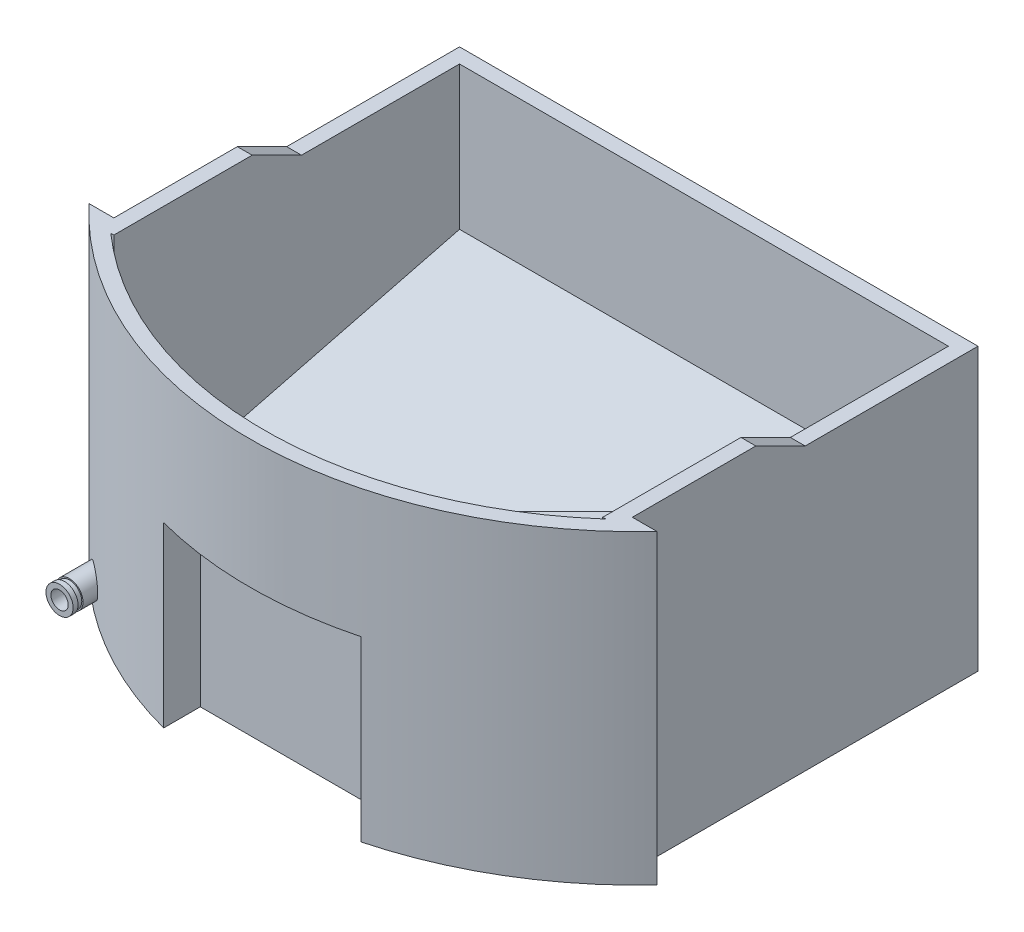
SolidWorks part; units mm, degrees
ref_plane "Front Plane" through (0, 0, 0) normal (0, 0, 1) x (1, 0, 0)
ref_plane "Top Plane" through (0, 0, 0) normal (0, 1, 0) x (1, 0, 0)
ref_plane "Right Plane" through (0, 0, 0) normal (1, 0, 0) x (0, 0, -1)
sketch "Sketch4" plane through (0, 0, 0) normal (0, 1, 0) x (1, 0, 0)
  line L0 (-6.35, 0) -> (139.7, 0)
  line L1 (0, 0) -> (133.35, 0)
  line L2 (0, 0) -> (0, 88.9)
  line L3 (0, 88.9) -> (133.35, 88.9)
  line L4 (133.35, 0) -> (133.35, 88.9)
  arc A1 (-6.35, 0) -> (139.7, 0) centre (66.675, 68.1037) ccw
  point P6 (66.675, -31.75)
  point P9 (66.675, 0)
  dimension "D1" = 133.35
  dimension "D2" = 88.9
  dimension "D3" = 146.05
  dimension "D4" = 6.35
  dimension "D5" = 31.75
extrude "Boss-Extrude2" add sketch "Sketch4" along normal blind 78.74 contours L0 A1 | L0 L4 L3 L2 region at (66.675, 0, 12.8907) region at (66.675, 0, -44.45)
sketch "Sketch5" plane through (0, 0, 0) normal (1, 0, 0) x (0, 0, -1)
  line L0 (0, 78.74) -> (88.9, 78.74) construction
  line L1 (0, 78.74) -> (88.9, 78.74)
  line L2 (88.9, 78.74) -> (88.9, 72.39)
  line L3 (88.9, 78.74) -> (88.9, 0) construction
  line L4 (88.9, 72.39) -> (44.45, 72.39)
  line L5 (44.45, 72.39) -> (31.75, 78.74)
  line L6 (31.75, 78.74) -> (88.9, 78.74)
  dimension "D1" = 12.7
  dimension "D2" = 44.45
  dimension "D3" = 6.35
extrude "Cut-Extrude4" cut sketch "Sketch5" along normal through all contours L2 L4 L5 L6
ref_plane "Plane1" through (3.81, 0, 0) normal (1, 0, 0) x (0, 0, -1)
ref_plane "Plane2" through (129.54, 0, 0) normal (1, 0, 0) x (0, 0, -1)
ref_plane "Plane3" through (0, 0, -85.09) normal (0, 0, -1) x (-1, 0, 0)
ref_plane "Plane4" through (0, 15.24, 0) normal (0, 1, 0) x (1, 0, 0)
ref_plane "Plane5" through (0, 0, 28.448) normal (0, 0, 1) x (1, 0, 0)
ref_plane "Plane6" through (8.89, 0, 0) normal (1, 0, 0) x (0, 0, -1)
ref_plane "Plane7" through (0, 0, -5.08) normal (0, 0, 1) x (1, 0, 0)
shell "Shell1" thickness 3.81 removed face at (66.675, 78.74, -5.2917) removed face at (66.675, 75.565, -38.1) removed face at (66.675, 72.39, -66.675)
sketch "Sketch8" plane through (0, 15.24, 0) normal (0, 1, 0) x (1, 0, 0)
  line L0 (0, 88.9) -> (133.35, 88.9) construction
  line L1 (133.35, 0) -> (133.35, 88.9) construction
  line L2 (-6.35, 0) -> (139.7, 0) construction
  line L3 (0, 0) -> (0, 88.9) construction
  line L4 (0, 88.9) -> (133.35, 88.9)
  line L5 (133.35, 0) -> (133.35, 88.9)
  line L6 (-6.35, 0) -> (139.7, 0)
  line L7 (0, 0) -> (0, 88.9)
  arc A0 (-6.35, 0) -> (139.7, 0) centre (66.675, 68.1037) ccw construction
  arc A1 (-6.35, 0) -> (139.7, 0) centre (66.675, 68.1037) ccw
extrude "fill in tube area" add sketch "Sketch8" against normal up to surface (15.24 mm away) contours L7 L6 L5 L4 | A1 L6 region at (66.675, 15.24, -44.45) up to plane "Top Plane"
sketch "Sketch7" plane through (3.81, 0, 0) normal (1, 0, 0) x (0, 0, -1)
  line L0 (-28.448, 78.74) -> (0, 15.24)
  line L1 (-28.448, 43.307) -> (-28.448, -43.307) construction
  line L2 (66.3575, 15.24) -> (-66.3575, 15.24) construction
  line L3 (0, 43.307) -> (0, -43.307) construction
  line L4 (0, 15.24) -> (-28.448, 15.24)
  line L5 (-28.448, 15.24) -> (-28.448, 78.74)
  line L6 (0, 78.74) -> (-31.75, 78.74) construction
extrude "Front inner slope" add sketch "Sketch7" along normal up to surface (125.73 mm away) up to plane "Plane2"
sketch "Sketch11" plane through (0, 15.24, 0) normal (0, 1, 0) x (1, 0, 0)
  line L0 (3.81, -43.307) -> (3.81, 43.307) construction
  line L1 (-6.35, 0) -> (139.7, 0) construction
  circle A0 centre (6.35, 2.54) radius 2.2225
  dimension "D1" = 4.445
  dimension "D2" = 2.54
  dimension "D3" = 2.54
extrude "Cut-Extrude6" cut sketch "Sketch11" against normal blind 10.16
sketch "Sketch12" plane through (0, 0, -85.09) normal (0, 0, -1) x (-1, 0, 0)
  line L0 (-129.54, 35.56) -> (-8.89, 15.24)
  line L1 (-129.54, 43.307) -> (-129.54, -43.307) construction
  line L2 (-8.89, 43.307) -> (-8.89, -43.307) construction
  line L3 (66.3575, 15.24) -> (-66.3575, 15.24) construction
  line L4 (-8.89, 15.24) -> (-129.54, 15.24)
  line L5 (-129.54, 15.24) -> (-129.54, 35.56)
  dimension "D1" = 20.32
extrude "Inner Slope 1" add sketch "Sketch12" against normal up to surface (113.538 mm away) up to plane "Plane5"
sketch "Sketch9" plane through (0, 15.24, 0) normal (0, 1, 0) x (1, 0, 0)
  line L2 (-6.35, 0) -> (-6.35, -28.448)
  line L3 (-43.307, -28.448) -> (43.307, -28.448) construction
  line L4 (-6.35, -28.448) -> (41.2087, -28.448)
  line L5 (139.7, -28.448) -> (139.7, 0)
  line L6 (92.1413, -28.448) -> (139.7, -28.448)
  arc A0 (-6.35, 0) -> (139.7, 0) centre (66.675, 68.1037) ccw construction
  arc A1 (-6.35, 0) -> (41.2087, -28.448) centre (66.675, 68.1037) ccw
  arc A2 (92.1413, -28.448) -> (139.7, 0) centre (66.675, 68.1037) ccw
extrude "Remove extra inner slope material" cut sketch "Sketch9" along normal through all
sketch "Sketch13" plane through (3.81, 0, 0) normal (1, 0, 0) x (0, 0, -1)
  line L0 (85.09, 35.56) -> (5.08, 15.24)
  line L1 (85.09, -39.8145) -> (85.09, 39.8145) construction
  line L2 (5.08, 43.307) -> (5.08, -43.307) construction
  line L3 (66.3575, 15.24) -> (-66.3575, 15.24) construction
  line L4 (5.08, 15.24) -> (85.09, 15.24)
  line L5 (85.09, 15.24) -> (85.09, 35.56)
  dimension "D1" = 20.32
extrude "Inner Slope 2" add sketch "Sketch13" along normal up to surface (125.73 mm away) up to plane "Plane2"
sketch "Sketch14" plane through (0, 0, 0) normal (0, 0, 1) x (1, 0, 0)
  line L1 (66.3575, 15.24) -> (-66.3575, 15.24) construction
  line L2 (3.81, -43.307) -> (3.81, 43.307) construction
  circle A0 centre (6.35, 6.985) radius 2.2225
  dimension "D3" = 4.445
  dimension "D1" = 2.54
  dimension "D2" = 8.255
extrude "Cut-Extrude7" cut sketch "Sketch14" against normal blind 4.826 and the other way through all
sketch "Sketch15" plane through (0, 0, 0) normal (0, 1, 0) x (1, 0, 0)
  line L0 (0, 88.9) -> (133.35, 88.9) construction
  line L1 (19.05, 88.9) -> (23.368, 88.9)
  line L2 (19.05, 88.9) -> (19.05, -6.35)
  line L3 (19.05, -6.35) -> (23.368, -6.35)
  line L4 (23.368, 88.9) -> (23.368, -6.35)
  line L5 (133.35, 0) -> (133.35, 88.9) construction
  line L6 (114.3, 88.9) -> (109.982, 88.9)
  line L7 (114.3, 88.9) -> (114.3, -6.35)
  line L8 (114.3, -6.35) -> (109.982, -6.35)
  line L9 (109.982, 88.9) -> (109.982, -6.35)
  line L10 (0, 0) -> (0, 88.9) construction
  line L12 (-6.35, 0) -> (139.7, 0) construction
  dimension "D1" = 4.318
  dimension "D2" = 4.318
  dimension "D3" = 19.05
  dimension "D4" = 19.05
  dimension "D5" = 6.35
extrude "rails" cut sketch "Sketch15" along normal blind 3.556
ref_plane "Plane8" through (0, 0, 19.05) normal (0, 0, 1) x (1, 0, 0)
sketch "Sketch16" plane through (0, 0, 0) normal (0, 1, 0) x (1, 0, 0)
  line L0 (-43.307, -19.05) -> (43.307, -19.05) construction
  line L2 (41.275, -24.5204) -> (41.275, -19.05)
  line L3 (41.275, -19.05) -> (92.075, -19.05)
  line L4 (92.075, -24.5204) -> (92.075, -19.05)
  arc A0 (3.81, -4.5075) -> (124.3293, -8.7102) centre (66.675, 68.1037) ccw construction
  arc A1 (41.275, -24.5204) -> (92.075, -24.5204) centre (66.675, 68.1037) ccw
  arc A2 (-6.35, 0) -> (139.7, 0) centre (66.675, 68.1037) ccw construction
  point P10 (66.675, -19.05)
  point P14 (66.675, -31.75)
  dimension "D1" = 50.8
extrude "Inner hand grip" cut sketch "Sketch16" along normal blind 57.15
sketch "Sketch17" plane through (0, 0, 0) normal (0, 1, 0) x (1, 0, 0)
  line L0 (41.275, -24.5204) -> (41.275, -28.4655)
  line L1 (92.075, -24.5204) -> (92.075, -28.4655)
  arc A0 (41.275, -24.5204) -> (92.075, -24.5204) centre (66.675, 68.1037) ccw
  arc A1 (3.81, -4.5075) -> (124.3293, -8.7102) centre (66.675, 68.1037) ccw construction
  arc A2 (41.275, -28.4655) -> (92.075, -28.4655) centre (66.675, 68.1037) ccw
  arc A3 (-6.35, 0) -> (139.7, 0) centre (66.675, 68.1037) ccw construction
  point P9 (66.675, -31.75)
  point P13 (66.675, -27.94)
  dimension "D1" = 50.8
extrude "Outer hand grip" cut sketch "Sketch17" along normal blind 45.72
sketch "Sketch18" plane through (0, 0, 0) normal (0, 0, 1) x (1, 0, 0)
  circle A0 centre (6.35, 6.985) radius 2.2225 construction
  circle A1 centre (6.35, 6.985) radius 2.2225
  circle A2 centre (6.35, 6.985) radius 3.4925
  dimension "D1" = 6.985
extrude "Boss-Extrude3" add sketch "Sketch18" along normal blind 20.32
sketch "Sketch19" plane through (0, 0, 19.05) normal (0, 0, 1) x (1, 0, 0)
  circle A0 centre (6.35, 6.985) radius 3.175
  circle A1 centre (6.35, 6.985) radius 3.4925 construction
  circle A3 centre (6.35, 6.985) radius 3.4925
  dimension "D2" = 6.35
extrude "Cut-Extrude8" cut sketch "Sketch19" against normal blind 1.27
sketch "Sketch20" plane through (3.81, 0, 0) normal (1, 0, 0) x (0, 0, -1)
  line L0 (4.699, 9.1745) -> (5.08, 9.1745)
  line L1 (5.08, 9.1745) -> (5.08, 4.6025)
  line L2 (5.08, 4.6025) -> (0.1806, 4.6025)
  line L3 (0.1806, 4.6025) -> (4.699, 9.1745)
  line L4 (0, 0) -> (88.9, 0) construction
  line L5 (0, 43.307) -> (0, -43.307) construction
  point P8 (0, 0)
  point P9 (0, 0)
  dimension "D1" = 0.381
  dimension "D2" = 4.572
  dimension "D3" = 4.8994
  dimension "D4" = 4.6025
  dimension "D5" = 5.08
extrude "Boss-Extrude4" add sketch "Sketch20" along normal blind 5.08
